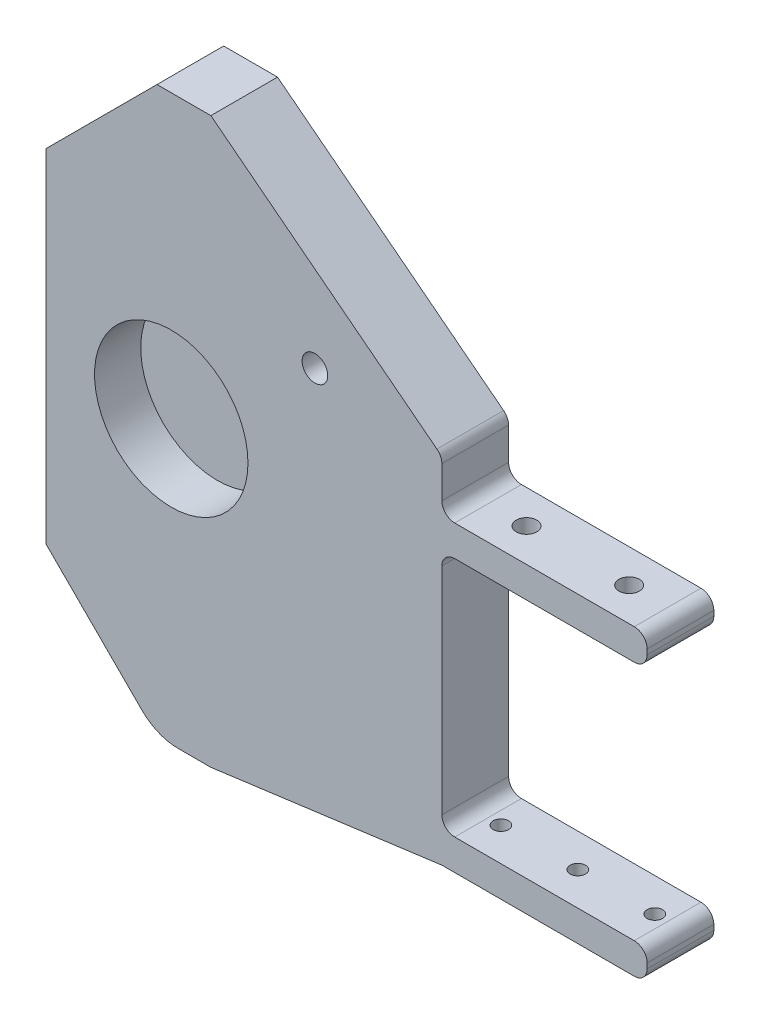
SolidWorks part; units mm, degrees
material "5052-H36"
ref_plane "Plano frontal" through (0, 0, 0) normal (0, 0, 1) x (1, 0, 0)
ref_plane "Plano superior" through (0, 0, 0) normal (0, 1, 0) x (1, 0, 0)
ref_plane "Plano direito" through (0, 0, 0) normal (1, 0, 0) x (0, 0, -1)
sketch "Esboço1" plane through (0, 0, 0) normal (0, 0, 1) x (1, 0, 0)
  line L0 (79.1281, 0) -> (0, 0) construction
  line L3 (4.9801, 55) -> (32.742, 55)
  line L6 (32.742, 55) -> (-22.7817, 55)
  line L12 (-22.7817, 55) -> (-44.3754, 33.4063)
  line L14 (-44.3754, -33.4063) -> (-22.7817, -55)
  line L15 (-22.7817, -55) -> (32.742, -55)
  line L18 (393.8557, 316.0739) -> (396.402, 318.6203) [skipped]
  line L19 (55, 501.996) -> (55, 520.8093) [skipped]
  line L20 (-316.0739, 393.8557) -> (-318.6203, 396.402) [skipped]
  line L21 (32.742, 55) -> (32.742, 10)
  line L22 (32.742, -49) -> (32.742, -55)
  line L23 (32.742, -49) -> (72.742, -49)
  line L25 (32.742, -43) -> (72.742, -43)
  line L26 (72.742, -49) -> (72.742, -43)
  line L27 (32.742, 4) -> (32.742, -43)
  line L28 (32.742, 4) -> (72.742, 4)
  line L30 (32.742, 10) -> (72.742, 10)
  line L31 (72.742, 4) -> (72.742, 10)
  line L32 (-44.3754, 33.4063) -> (-44.3754, -33.4063)
  line L34 (-55, 7.7563) -> (-55, -6.3461) [skipped]
  circle A0 centre (0, 0) radius 15 construction
  arc A3 (4.9801, 55) -> (0, -55.225) centre (0, 0) ccw construction
  point P14 (4.9801, 55)
  dimension "D1" = 30
  dimension "D5" = 110
  dimension "D6" = 40
  dimension "D7" = 6
  dimension "D8" = 6
  dimension "D9" = 45
extrude "Ressalto-extrusão1" add sketch "Esboço1" along normal mid plane 13 contours L14 L15 L3 L6 L12 A0 region at (-0.7875, -1.1016, 0)
sketch "Esboço2" plane through (0, 0, 6.5) normal (0, 0, 1) x (1, 0, 0)
  circle A1 centre (-20, 0) radius 14.95
  dimension "D1" = 29.9
  dimension "D2" = 20
extrude "Corte-extrusão1" cut sketch "Esboço2" against normal blind 9
sketch "Esboço3" plane through (0, 0, 6.5) normal (0, 0, 1) x (1, 0, 0)
  line L0 (-22.7817, -55) -> (32.742, -55) construction
  line L1 (-12.2817, -55) -> (32.742, -49)
  line L2 (32.742, -49) -> (32.742, -55)
  line L3 (32.742, -55) -> (-12.2817, -55)
  line L4 (-12.2817, -55) -> (-12.2817, 66.3095) construction
  line L6 (32.742, 10) -> (72.742, 10) construction
  line L11 (32.742, 55) -> (-12.2817, 55)
  line L12 (-12.2817, 55) -> (32.742, 20)
  line L13 (32.742, 20) -> (32.742, 55)
  circle A0 centre (8, 22.5) radius 2.5
  point P0 (-12.2817, -55)
  dimension "D2" = 5
  dimension "D1" = 10.5
  dimension "D3" = 22.5
  dimension "D4" = 28
  dimension "D5" = 10
extrude "Corte-extrusão2" cut sketch "Esboço3" against normal blind 13
fillet "Filete1" radius 10 1 edges at (-22.7817, -55, 0)
sketch "Esboço4" plane through (0, 0, -6.5) normal (0, 0, -1) x (-1, 0, 0)
  line L0 (44.3754, 33.4063) -> (44.3754, -33.4063) construction
  circle A0 centre (36.3754, 8.4063) radius 2
  circle A1 centre (12.9554, -16.5937) radius 2
  circle A2 centre (22.3754, -27.5937) radius 2
  dimension "D1" = 4
  dimension "D2" = 25
  dimension "D3" = 8
  dimension "D4" = 23.42
  dimension "D5" = 25
  dimension "D6" = 36
  dimension "D7" = 14
extrude "Corte-extrusão3" cut sketch "Esboço4" against normal blind 10
sketch "Esboço6" plane through (0, 10, 0) normal (0, 1, 0) x (1, 0, 0)
  circle A0 centre (42.742, -0.0016) radius 2
  circle A1 centre (62.742, -0.0016) radius 2
  circle A2 centre (42.742, -0.0016) radius 2 construction
  dimension "D1" = 20
extrude "Corte-extrusão4" cut sketch "Esboço6" against normal blind 10
sketch "Esboço7" plane through (0, -49, 0) normal (0, -1, 0) x (1, 0, 0)
  line L0 (32.742, -6.5) -> (72.742, -6.5) construction
  line L1 (37.742, 0) -> (67.742, 0) construction
  line L2 (72.742, 6.5) -> (72.742, -6.5) construction
  circle A0 centre (37.742, 0) radius 1.5
  circle A1 centre (52.742, 0) radius 1.5
  circle A2 centre (67.742, 0) radius 1.5
  dimension "D1" = 3
  dimension "D2" = 6.5
  dimension "D3" = 5
  dimension "D4" = 20
  dimension "D5" = 35
extrude "Corte-extrusão5" cut sketch "Esboço7" against normal blind 10
fillet "Filete2" radius 2.5 8 edges at (72.742, -49, 0) (72.742, -43, 0) (72.742, 4, 0) (72.742, 10, 0) (32.742, 20, 0) (32.742, -43, 0) (32.742, 10, 0) (32.742, 4, 0)
